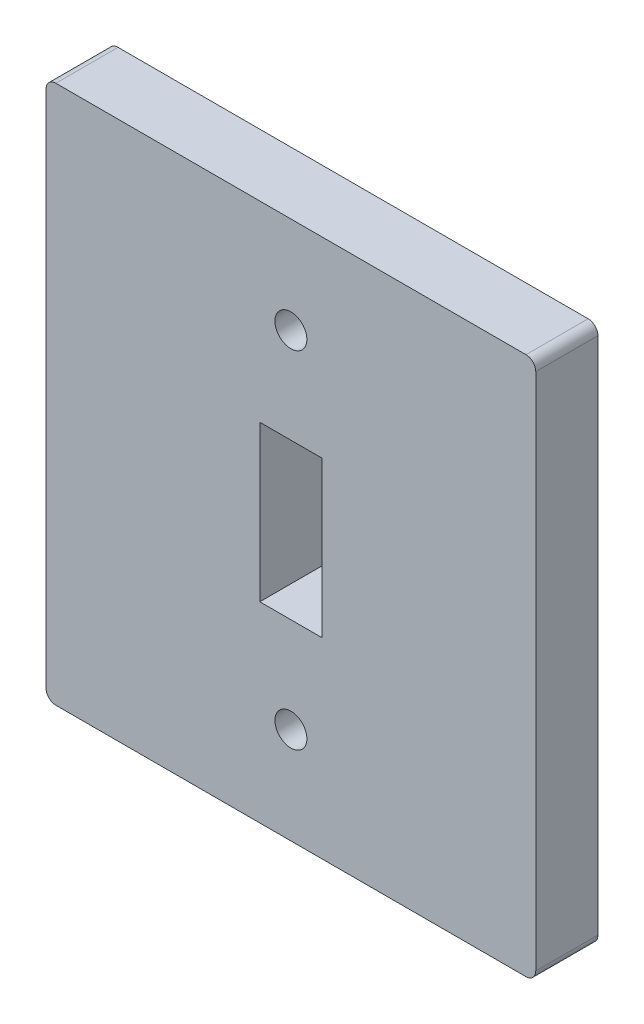
SolidWorks part; units mm, degrees
ref_plane "Front Plane" through (0, 0, 0) normal (0, 0, 1) x (1, 0, 0)
ref_plane "Top Plane" through (0, 0, 0) normal (0, 1, 0) x (1, 0, 0)
ref_plane "Right Plane" through (0, 0, 0) normal (1, 0, 0) x (0, 0, -1)
sketch "Sketch1" plane through (0, 0, 0) normal (0, 0, 1) x (1, 0, 0)
  line L0 (50, -110) -> (50, -90.31) construction
  line L1 (0, 0) -> (100, 0)
  line L2 (0, 0) -> (0, -110)
  line L3 (0, -110) -> (100, -110)
  line L4 (100, 0) -> (100, -110)
  line L5 (50, 0) -> (50, -110) construction
  line L6 (50, -39.125) -> (56.35, -39.125)
  line L8 (56.35, -70.875) -> (50, -70.875)
  line L9 (50, -70.875) -> (43.65, -70.875)
  line L10 (43.65, -70.875) -> (43.65, -39.125)
  line L11 (43.65, -39.125) -> (50, -39.125)
  line L12 (50, 0) -> (50, -19.69) construction
  line L13 (100, -55) -> (0, -55) construction
  line L14 (56.35, -39.125) -> (56.35, -55)
  line L15 (56.35, -55) -> (56.35, -70.875)
  dimension "D6" = 100
  dimension "D1" = 110
  dimension "D2" = 31.75
  dimension "D3" = 12.7
  dimension "D4" = 19.69
  dimension "D5" = 19.69
extrude "Boss-Extrude2" add sketch "Sketch1" along normal blind 12.7
sketch "Sketch8" plane through (0, 0, 0) normal (0, 0, -1) x (-1, 0, 0)
  line L0 (0, -110) -> (-100, -110) construction
  line L1 (-50, -110) -> (-50, -90.31) construction
  dimension "D1" = 19.69
hole_wizard "CSK for 1/4 Flat Head Machine Screw3" positions "Sketch9" profile "Sketch10" countersink size "1/4" standard "ANSI Inch" end condition through all
sketch "Sketch9" plane through (0, 0, 0) normal (0, 0, -1) x (-1, 0, 0)
  point P0 (-50, -90.31)
sketch "Sketch10" plane through (50, -90.31, 0) normal (1, 0, 0) x (0, 1, 0)
  line L0 (0, 0) -> (0, 12.7)
  line L1 (0, 12.7) -> (3.2639, 12.7)
  line L2 (3.2639, 12.7) -> (3.2639, 3.6524)
  line L3 (3.2639, 3.6524) -> (6.4389, 0)
  line L5 (6.4389, 0) -> (0, 0)
  line L6 (-3.2639, 3.6524) -> (-6.4389, 0) construction
  line L11 (0, -6.35) -> (0, 107.95) construction
  dimension "Thru Hole Dia." = 6.5278
  dimension "Thru Hole Depth" = 12.7
  dimension "Near C'Sink Dia." = 12.8778
  dimension "Near C'Sink Angle" = 82
sketch "Sketch11" plane through (0, 0, 0) normal (0, 0, -1) x (-1, 0, 0)
  line L0 (-50, 0) -> (-50, -19.69)
  line L1 (-100, 0) -> (0, 0) construction
  dimension "D1" = 19.69
hole_wizard "CSK for 1/4 Flat Head Machine Screw4" positions "Sketch12" profile "Sketch13" countersink size "1/4" standard "ANSI Inch" end condition through all
sketch "Sketch12" plane through (0, 0, 0) normal (0, 0, -1) x (-1, 0, 0)
  point P0 (-50, -19.69)
sketch "Sketch13" plane through (50, -19.69, 0) normal (1, 0, 0) x (0, 1, 0)
  line L0 (0, 0) -> (0, 12.7)
  line L1 (0, 12.7) -> (3.2639, 12.7)
  line L2 (3.2639, 12.7) -> (3.2639, 3.6524)
  line L3 (3.2639, 3.6524) -> (6.4389, 0)
  line L5 (6.4389, 0) -> (0, 0)
  line L6 (-3.2639, 3.6524) -> (-6.4389, 0) construction
  line L11 (0, -6.35) -> (0, 107.95) construction
  dimension "Thru Hole Dia." = 6.5278
  dimension "Thru Hole Depth" = 12.7
  dimension "Near C'Sink Dia." = 12.8778
  dimension "Near C'Sink Angle" = 82
fillet "Fillet1" radius 2 4 edges at (0, 0, 6.35) (100, 0, 6.35) (0, -110, 6.35) (100, -110, 6.35)
